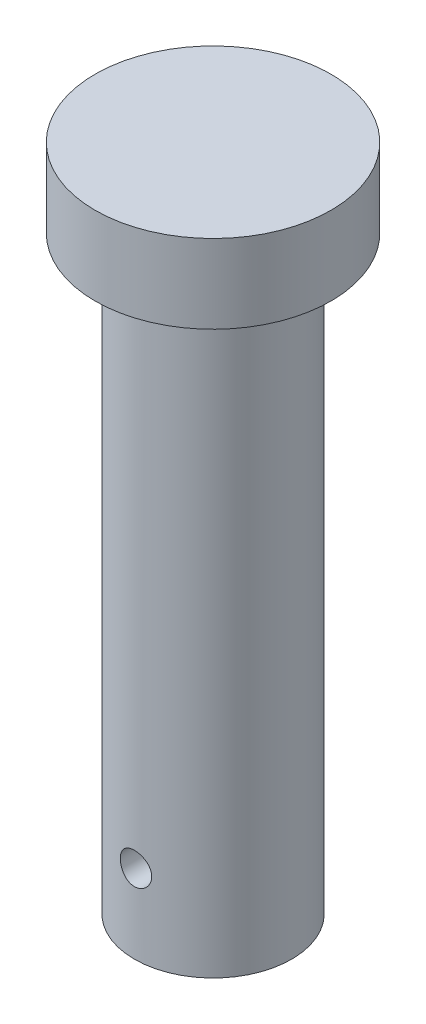
SolidWorks part; units mm, degrees
ref_plane "Front Plane" through (0, 0, 0) normal (0, 0, 1) x (1, 0, 0)
ref_plane "Top Plane" through (0, 0, 0) normal (0, 1, 0) x (1, 0, 0)
ref_plane "Right Plane" through (0, 0, 0) normal (1, 0, 0) x (0, 0, -1)
sketch "Sketch1" plane through (0, 0, 0) normal (0, 1, 0) x (1, 0, 0)
  circle A0 centre (0, 0) radius 10
  dimension "D1" = 20
extrude "Boss-Extrude1" add sketch "Sketch1" along normal blind 75
sketch "Sketch2" plane through (0, 75, 0) normal (0, 1, 0) x (1, 0, 0)
  circle A0 centre (0, 0) radius 15
  dimension "D1" = 30
extrude "Boss-Extrude2" add sketch "Sketch2" along normal blind 10
sketch "Sketch3" plane through (0, 0, 0) normal (0, 0, 1) x (1, 0, 0)
  circle A0 centre (0, 10) radius 2
  dimension "D2" = 4
  dimension "D1" = 10
extrude "Cut-Extrude1" cut sketch "Sketch3" against normal blind 30 draft 1 and the other way blind 30
